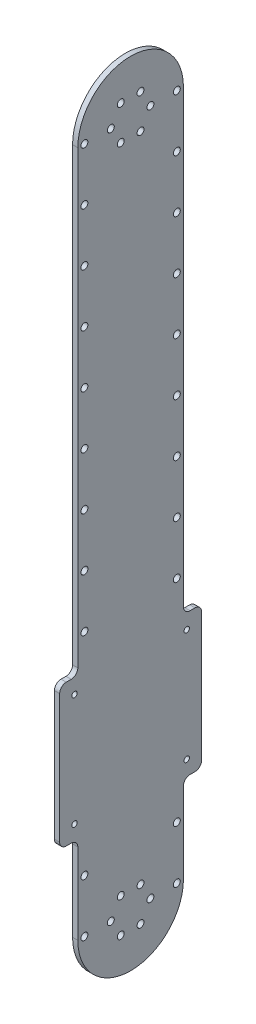
SolidWorks part; units mm, degrees
ref_plane "Front Plane" through (0, 0, 0) normal (1, 0, 0) x (0, 1, 0)
ref_plane "Top Plane" through (0, 0, 0) normal (0, 0, 1) x (0, 1, 0)
ref_plane "Right Plane" through (0, 0, 0) normal (0, 1, 0) x (-1, 0, 0)
sketch "Sketch1" plane through (0, 0, 0) normal (1, 0, 0) x (0, 1, 0)
  line L0 (-208, 0) -> (208, 0) construction
  line L1 (-208, 32) -> (208, 32)
  line L2 (-208, -32) -> (208, -32)
  arc A0 (-208, 32) -> (-208, -32) centre (-208, 0) ccw
  arc A1 (208, -32) -> (208, 32) centre (208, 0) ccw
  point P2 (0, 0)
  point P7 (0, 0)
  dimension "D2" = 32
  dimension "D1" = 416
extrude "Boss-Extrude1" add sketch "Sketch1" along normal mid plane 3.175
sketch "Sketch2" plane through (1.5875, 0, 0) normal (1, 0, 0) x (0, 1, 0)
  arc A0 (-208, 32) -> (-208, -32) centre (-208, 0) ccw construction
  arc A1 (-208, 32) -> (-208, -32) centre (-208, 0) ccw construction
  circle A2 centre (-208, 12) radius 2.1
  circle A3 centre (-197.6077, 6) radius 2.1
  circle A4 centre (-197.6077, -6) radius 2.1
  circle A5 centre (-208, -12) radius 2.1
  circle A6 centre (-218.3923, -6) radius 2.1
  circle A7 centre (-218.3923, 6) radius 2.1
  dimension "D1" = 4.2
  dimension "D2" = 12
  dimension "D3" = 6
extrude "Cut-Extrude1" cut sketch "Sketch2" against normal through all
sketch "Sketch3" plane through (1.5875, 0, 0) normal (1, 0, 0) x (0, 1, 0)
  line L0 (-208, -32) -> (208, -32) construction
  line L1 (-146, -34) -> (-78, -34) construction
  line L2 (-146, -34) -> (-146, 34) construction
  line L3 (-146, 34) -> (-78, 34) construction
  line L4 (-78, -34) -> (-78, 34) construction
  line L5 (-146, -34) -> (-78, 34) construction
  line L6 (-146, 34) -> (-78, -34) construction
  line L7 (-155, -43) -> (-69, -43)
  line L8 (-155, -43) -> (-155, 43)
  line L9 (-155, 43) -> (-69, 43)
  line L10 (-69, -43) -> (-69, 43)
  line L11 (-155, -43) -> (-69, 43) construction
  line L12 (-155, 43) -> (-69, -43) construction
  line L13 (208, 32) -> (-208, 32) construction
  line L14 (-208, -32) -> (208, -32)
  line L15 (208, 32) -> (-208, 32)
  arc A0 (-208, 32) -> (-208, -32) centre (-208, 0) ccw construction
  arc A1 (-208, 32) -> (-208, -32) centre (-208, 0) ccw construction
  circle A2 centre (-146, 34) radius 1.65
  circle A3 centre (-78, 34) radius 1.65
  circle A4 centre (-78, -34) radius 1.65
  circle A5 centre (-146, -34) radius 1.65
  point P0 (-112, 0)
  point P10 (-112, 0)
  line M21 (-208, -32) -> (208, -32)
  line M23 (208, 32) -> (-208, 32)
  dimension "D4" = 3.3
  dimension "D1" = 68
  dimension "D2" = 68
  dimension "D3" = 96
  dimension "D6" = 86
  dimension "D7" = 86
  dimension "D5" = 4
extrude "Boss-Extrude2" add sketch "Sketch3" against normal up to surface (3.175 mm away) contours L10 L8 M21 M23 | A2 | A3 | A4 | A5 | L9 L10 L7 L8 region at (1.5875, -112, 0) region at (1.5875, -146, 34) region at (1.5875, -78, 34) region at (1.5875, -78, -34) region at (1.5875, -146, -34) up to face at (-1.5875, -208, 9.9)
fillet "Fillet1" radius 4 8 edges at (0, -155, 43) (0, -155, 32) (0, -69, 43) (0, -69, 32) (0, -155, -32) (0, -155, -43) (0, -69, -43) (0, -69, -32)
sketch "Sketch4" plane through (1.5875, 0, 0) normal (1, 0, 0) x (0, 1, 0)
  arc A0 (208, -32) -> (208, 32) centre (208, 0) ccw construction
  arc A1 (208, -32) -> (208, 32) centre (208, 0) ccw construction
  circle A2 centre (208, 12) radius 2.1
  circle A3 centre (218.3923, 6) radius 2.1
  circle A4 centre (218.3923, -6) radius 2.1
  circle A5 centre (208, -12) radius 2.1
  circle A6 centre (197.6077, -6) radius 2.1
  circle A7 centre (197.6077, 6) radius 2.1
  dimension "D1" = 4.2
  dimension "D2" = 12
  dimension "D3" = 6
extrude "Cut-Extrude2" cut sketch "Sketch4" against normal through all
sketch "Sketch5" plane through (1.5875, 0, 0) normal (1, 0, 0) x (0, 1, 0)
  line L0 (-159, 32) -> (-208, 32) construction
  line L1 (-208, 0) -> (0, 0) construction
  circle A0 centre (-208, 28) radius 2.1
  arc A1 (-208, 32) -> (-208, -32) centre (-208, 0) ccw construction
  arc A2 (-208, 32) -> (-208, -32) centre (-208, 0) ccw construction
  circle A3 centre (-176, 28) radius 2.1
  circle A4 centre (-144, 28) radius 2.1
  circle A5 centre (-112, 28) radius 2.1
  circle A6 centre (-80, 28) radius 2.1
  circle A7 centre (-48, 28) radius 2.1
  circle A8 centre (-16, 28) radius 2.1
  circle A9 centre (16, 28) radius 2.1
  circle A10 centre (48, 28) radius 2.1
  circle A11 centre (80, 28) radius 2.1
  circle A12 centre (112, 28) radius 2.1
  circle A13 centre (144, 28) radius 2.1
  circle A14 centre (176, 28) radius 2.1
  circle A39 centre (176, -28) radius 2.1
  circle A40 centre (144, -28) radius 2.1
  circle A41 centre (112, -28) radius 2.1
  circle A42 centre (80, -28) radius 2.1
  circle A43 centre (48, -28) radius 2.1
  circle A44 centre (16, -28) radius 2.1
  circle A45 centre (-16, -28) radius 2.1
  circle A46 centre (-48, -28) radius 2.1
  circle A47 centre (-80, -28) radius 2.1
  circle A48 centre (-112, -28) radius 2.1
  circle A49 centre (-144, -28) radius 2.1
  circle A50 centre (-176, -28) radius 2.1
  circle A51 centre (-208, -28) radius 2.1
  circle A52 centre (208, 28) radius 2.1
  circle A53 centre (208, -28) radius 2.1
  dimension "D1" = 4.2
  dimension "D2" = 4
  dimension "D4" = 32
  dimension "D3" = 14
extrude "Cut-Extrude3" cut sketch "Sketch5" against normal through all contours A0 | A3 | A51 | A50 | A46 | A45 | A7 | A8 | A9 | A44 | A43 | A42 | A11 | A12 | A41 | A40 | A13 | A39 | A14 | A52 | A53 | A10
